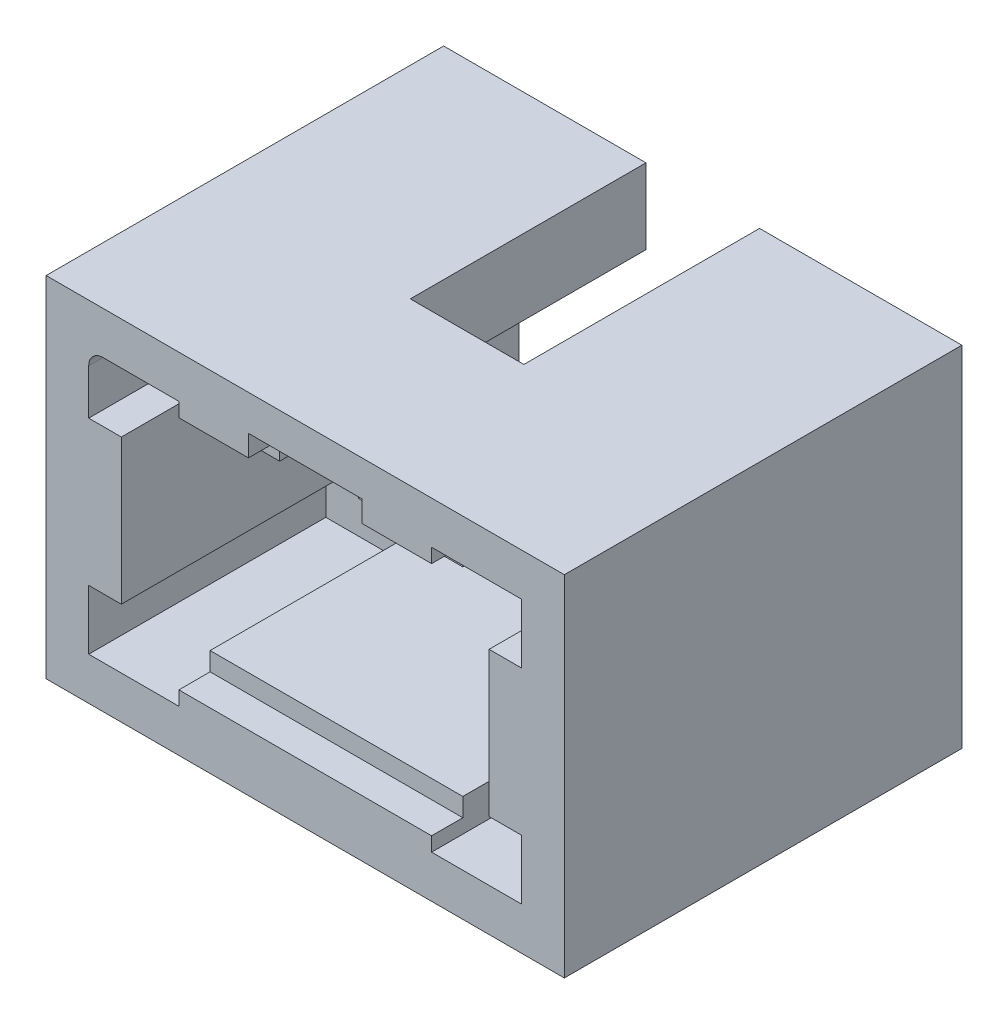
SolidWorks part; units mm, degrees
ref_plane "Front Plane" through (0, 0, 0) normal (0, 0, 1) x (1, 0, 0)
ref_plane "Top Plane" through (0, 0, 0) normal (0, 1, 0) x (1, 0, 0)
ref_plane "Right Plane" through (0, 0, 0) normal (1, 0, 0) x (0, 0, -1)
sketch "Sketch1" plane through (0, 0, 0) normal (0, 0, 1) x (1, 0, 0)
  line L1 (-7.125, -4.15) -> (7.125, -4.15)
  line L2 (-7.125, -4.15) -> (-7.125, 4.15)
  line L3 (-7.125, 4.15) -> (7.125, 4.15)
  line L4 (7.125, -4.15) -> (7.125, 4.15)
  line L5 (-7.125, -4.15) -> (7.125, 4.15) construction
  line L6 (-7.125, 4.15) -> (7.125, -4.15) construction
  line L7 (-9.125, -6.15) -> (9.125, -6.15)
  line L8 (-9.125, -6.15) -> (-9.125, 6.15)
  line L9 (-9.125, 6.15) -> (9.125, 6.15)
  line L10 (9.125, -6.15) -> (9.125, 6.15)
  line L11 (-9.125, -6.15) -> (9.125, 6.15) construction
  line L12 (-9.125, 6.15) -> (9.125, -6.15) construction
  point P0 (0, 0)
  point P5 (0, 0)
  dimension "D1" = 8.3
  dimension "D2" = 14.25
  dimension "D3" = 2
  dimension "D4" = 2
extrude "Boss-Extrude1" add sketch "Sketch1" along normal blind 14
sketch "Sketch4" plane through (0, 0, 0) normal (0, 0, -1) x (-1, 0, 0)
  line L0 (-7.125, 4.15) -> (7.125, 4.15) construction
  line L1 (7.125, -4.15) -> (-7.125, -4.15) construction
  line L2 (-7.125, -4.15) -> (-7.125, 4.15) construction
  line L3 (7.125, 4.15) -> (7.125, -4.15) construction
  line L4 (-9.125, 6.15) -> (-9.125, -6.15)
  line L5 (-9.125, -6.15) -> (9.125, -6.15)
  line L6 (9.125, -6.15) -> (9.125, 6.15)
  line L7 (9.125, 6.15) -> (-9.125, 6.15)
  line L8 (-9.125, 6.15) -> (-9.125, -6.15)
  line L9 (-9.125, -6.15) -> (9.125, -6.15)
  line L10 (9.125, -6.15) -> (9.125, 6.15)
  line L11 (9.125, 6.15) -> (-9.125, 6.15)
  line L12 (-7.125, 4.15) -> (7.125, 4.15)
  line L13 (7.125, -4.15) -> (-7.125, -4.15)
  line L14 (-7.125, -4.15) -> (-7.125, 4.15)
  line L15 (7.125, 4.15) -> (7.125, -4.15)
  line L16 (0, 0) -> (0, 3.5) construction
  line L17 (-7.125, 2.55) -> (-6.475, 2.55)
  line L18 (-7.125, 2.55) -> (-7.125, -2.55)
  line L19 (-7.125, -2.55) -> (-6.475, -2.55)
  line L20 (-6.475, 2.55) -> (-6.475, -2.55)
  line L21 (-4.45, 4.15) -> (4.45, 4.15)
  line L22 (-4.45, 4.15) -> (-4.45, 3.5)
  line L23 (-4.45, 3.5) -> (4.45, 3.5)
  line L24 (4.45, 4.15) -> (4.45, 3.5)
  line L25 (0, 0) -> (-6.475, 0) construction
  line L26 (4.45, -4.15) -> (4.45, -3.5)
  line L27 (-7.125, -4.15) -> (7.125, -4.15)
  line L28 (-4.45, -4.15) -> (-4.45, -3.5)
  line L29 (-4.45, -3.5) -> (4.45, -3.5)
  line L30 (7.125, -4.15) -> (7.125, 4.15)
  line L31 (7.125, -2.55) -> (6.475, -2.55)
  line L32 (6.475, 2.55) -> (6.475, -2.55)
  line L33 (7.125, 2.55) -> (6.475, 2.55)
  point P8 (0, 0)
  dimension "D2" = 8.9
  dimension "D3" = 5.1
  dimension "D4" = 0.65
  dimension "D1" = 0
extrude "Boss-Extrude2" add sketch "Sketch4" against normal offset from surface (12.9 mm away) 1.1 contours L24 L12 L22 L23 | L29 L28 L13 L26 region at (0, 3.825, 0) region at (0, -3.825, 0) up to face at (0, 0, 14)
extrude "Boss-Extrude3" add sketch "Sketch4<3>" against normal up to surface (14 mm away) contours L20 L17 L14 L19 | L30 L33 L32 L31 region at (6.8, 0, 0) region at (-6.8, 0, 0) up to face at (0, 0, 14)
sketch "Sketch4<3>" plane through (0, 0, 0) normal (0, 0, -1) x (-1, 0, 0) same geometry as "Sketch4"
sketch "Sketch5" plane through (0, 0, 0) normal (0, 0, -1) x (-1, 0, 0)
  line L0 (9.125, 6.15) -> (-9.125, 6.15) construction
  line L1 (-2, 6.15) -> (2, 6.15)
  line L2 (-2, 6.15) -> (-2, 3.5)
  line L3 (-2, 3.5) -> (2, 3.5)
  line L4 (2, 6.15) -> (2, 3.5)
  line L5 (-4.45, 3.5) -> (4.45, 3.5) construction
  dimension "D1" = 4
extrude "Cut-Extrude2" cut sketch "Sketch5" against normal blind 8.3
sketch "Sketch6" plane through (0, 0, 0) normal (0, 0, -1) x (-1, 0, 0)
  line L0 (-4.45, -3.5) -> (4.45, -3.5) construction
  line L1 (6.475, 2.55) -> (6.475, -2.55) construction
  line L2 (-4.45, -3.5) -> (4.45, -3.5)
  line L3 (6.475, 2.55) -> (6.475, -2.55)
  line L5 (-6.475, 3.5) -> (6.475, 3.5)
  line L6 (-6.475, 3.5) -> (-6.475, -3.5)
  line L7 (-6.475, -3.5) -> (6.475, -3.5)
  line L8 (6.475, 3.5) -> (6.475, -3.5)
  line L9 (-6.475, 3.5) -> (6.475, -3.5) construction
  line L10 (-6.475, -3.5) -> (6.475, 3.5) construction
  line L11 (-7.125, 4.15) -> (7.125, 4.15)
  line L12 (-7.125, 4.15) -> (-7.125, -4.15)
  line L13 (-7.125, -4.15) -> (7.125, -4.15)
  line L14 (7.125, 4.15) -> (7.125, -4.15)
  line L15 (-7.125, 4.15) -> (7.125, -4.15) construction
  line L16 (-7.125, -4.15) -> (7.125, 4.15) construction
  point P4 (0, 0)
  point P9 (0, 0)
  line M12 (4.45, 3.5) -> (4.45, 4.15)
  line M13 (4.45, 4.15) -> (7.125, 4.15)
  line M14 (7.125, 4.15) -> (7.125, 2.55)
  line M15 (7.125, 2.55) -> (6.475, 2.55)
  line M17 (6.475, -2.55) -> (7.125, -2.55)
  line M18 (7.125, -2.55) -> (7.125, -4.15)
  line M19 (7.125, -4.15) -> (4.45, -4.15)
  line M20 (4.45, -4.15) -> (4.45, -3.5)
  line M22 (-4.45, -3.5) -> (-4.45, -4.15)
  line M23 (-4.45, -4.15) -> (-7.125, -4.15)
  line M24 (-7.125, -4.15) -> (-7.125, -2.55)
  line M25 (-7.125, -2.55) -> (-6.475, -2.55)
  line M27 (-6.475, 2.55) -> (-7.125, 2.55)
  line M28 (-7.125, 2.55) -> (-7.125, 4.15)
  line M29 (-7.125, 4.15) -> (-4.45, 4.15)
  line M30 (-4.45, 4.15) -> (-4.45, 3.5)
extrude "Boss-Extrude4" add sketch "Sketch6" against normal offset from surface (5.65 mm away) 8.35 contours L8 L7 M17 M20 M19 M18 | L5 L8 M15 M14 M13 M12 | L6 L5 M30 M29 M28 M27 | L7 L6 M25 M24 M23 M22 region at (6.0528, -3.6153, 0) region at (-6.0528, -3.6153, 0) region at (6.0528, 3.6153, 0) region at (-6.0528, 3.6153, 0) up to face at (0, 0, 14)
sketch "Sketch7" plane through (0, 0, 8.3) normal (0, 0, -1) x (-1, 0, 0)
  line L1 (-2, 3.5) -> (2, 3.5)
  line L2 (-2, 3.5) -> (-2, 4.9)
  line L3 (-2, 4.9) -> (2, 4.9)
  line L4 (-2, 6.15) -> (-2, 3.5)
  line L5 (-2, 3.5) -> (2, 3.5)
  line L6 (2, 3.5) -> (2, 6.15)
  line L7 (2, 6.15) -> (-2, 6.15)
  line L8 (-2, 6.15) -> (-2, 3.5)
  line L9 (-2, 3.5) -> (2, 3.5)
  line L10 (2, 3.5) -> (2, 6.15)
  line L11 (2, 6.15) -> (-2, 6.15)
  line L12 (2, 3.5) -> (2, 4.9)
  line M7 (-2, 6.15) -> (-2, 3.5)
  line M8 (-2, 3.5) -> (2, 3.5)
  line M9 (2, 3.5) -> (2, 6.15)
  dimension "D2" = 1.4
  dimension "D1" = 0
extrude "Cut-Extrude3" cut sketch "Sketch7" against normal through all contours L3 M7 M8 M9 region at (0, 4.2, 8.3)
sketch "Sketch8" plane through (0, 0, 14) normal (0, 0, 1) x (1, 0, 0)
  circle A0 centre (-7.125, 4.15) radius 0.5
  dimension "D1" = 1
extrude "Cut-Extrude4" cut sketch "Sketch8" against normal up to surface (8.35 mm away) up to face at (-6.0167, 3.4, 5.65)
mirror "Mirror1" about plane through (0, 0, 0) normal (0, 1, 0) of "Cut-Extrude4"
mirror "Mirror2" about plane through (0, 0, 0) normal (1, 0, 0) of "Mirror1"
sketch "Sketch9" plane through (0, 0, 14) normal (0, 0, 1) x (1, 0, 0)
  line L1 (-7.625, -4.65) -> (-4.45, -4.65)
  line L2 (-7.625, -4.65) -> (-7.625, -2.55)
  line L3 (-7.625, -2.55) -> (-4.45, -2.55)
  line L4 (-4.45, -4.65) -> (-4.45, -2.55)
  line L5 (-6.475, -2.55) -> (-7.125, -2.55) construction
  line L7 (-4.45, -3.5) -> (-4.45, -4.15) construction
  line L8 (-6.475, 0) -> (6.475, 0) construction
  line L9 (-6.475, -2.55) -> (-6.475, 2.55) construction
  line L10 (6.475, -2.55) -> (6.475, 2.55) construction
  line L11 (0, -6.15) -> (0, 6.15) construction
  line L12 (-9.125, -6.15) -> (9.125, -6.15) construction
  line L13 (9.125, 6.15) -> (-9.125, 6.15) construction
  line L14 (-7.625, 2.55) -> (-4.45, 2.55)
  line L15 (-4.45, 4.65) -> (-4.45, 2.55)
  line L16 (-7.625, 4.65) -> (-4.45, 4.65)
  line L17 (-7.625, 4.65) -> (-7.625, 2.55)
  line L18 (4.45, 4.65) -> (4.45, 2.55)
  line L19 (7.625, 4.65) -> (4.45, 4.65)
  line L20 (7.625, 4.65) -> (7.625, 2.55)
  line L21 (7.625, 2.55) -> (4.45, 2.55)
  line L22 (4.45, -4.65) -> (4.45, -2.55)
  line L23 (7.625, -2.55) -> (4.45, -2.55)
  line L24 (7.625, -4.65) -> (7.625, -2.55)
  line L25 (7.625, -4.65) -> (4.45, -4.65)
  arc A0 (-7.125, -3.65) -> (-6.625, -4.15) centre (-7.125, -4.15) ccw construction
  arc A1 (-7.125, -3.65) -> (-6.625, -4.15) centre (-7.125, -4.15) ccw
  arc M11 (6.625, 4.15) -> (7.125, 3.65) centre (7.125, 4.15) cw
  line M12 (7.125, 3.65) -> (7.125, 2.55)
  line M13 (7.125, 2.55) -> (6.475, 2.55)
  line M15 (6.475, -2.55) -> (7.125, -2.55)
  line M16 (7.125, -2.55) -> (7.125, -3.65)
  arc M17 (7.125, -3.65) -> (6.625, -4.15) centre (7.125, -4.15) cw
  line M18 (6.625, -4.15) -> (-6.625, -4.15)
  arc M19 (-6.625, -4.15) -> (-7.125, -3.65) centre (-7.125, -4.15) cw
  line M20 (-7.125, -3.65) -> (-7.125, -2.55)
  line M21 (-7.125, -2.55) -> (-6.475, -2.55)
  line M24 (-7.125, 2.55) -> (-7.125, 3.65)
  arc M25 (-7.125, 3.65) -> (-6.625, 4.15) centre (-7.125, 4.15) cw
  line M26 (-6.625, 4.15) -> (-2, 4.15)
  line M30 (2, 4.15) -> (6.625, 4.15)
extrude "Cut-Extrude5" cut sketch "Sketch9" against normal up to surface (8.35 mm away) contours L4 L3 M18 M21 M20 M19 | L1 L4 M18 M19 | L3 L2 M19 M20 | L17 L14 M25 M24 | L16 L15 M25 M26 | L24 L23 M17 M16 | L25 L22 M17 M18 | L23 L22 M15 M18 M17 M16 | L25 L24 M17 | L20 L19 M11 | L21 L20 M11 M12 | L19 L18 M11 M30 | L21 L18 M13 M12 M11 M30 | L2 L1 M19 | L4 L3 L2 L1 region at (-7.5133, -4.5383, 14) region at (5.9579, -3.4553, 14) region at (5.5939, -4.4065, 14) region at (-5.5939, -4.4065, 14) region at (-5.9579, -3.4553, 14) region at (-7.3873, -3.1588, 14) region at (7.5133, -4.5383, 14) region at (7.3873, -3.1588, 14) region at (-7.3873, 3.1588, 14) region at (-5.5939, 4.4065, 14) region at (5.5939, 4.4065, 14) region at (5.9579, 3.4553, 14) region at (7.5133, 4.5383, 14) region at (7.3873, 3.1588, 14) up to face at (-6.1898, -3.5219, 5.65)
